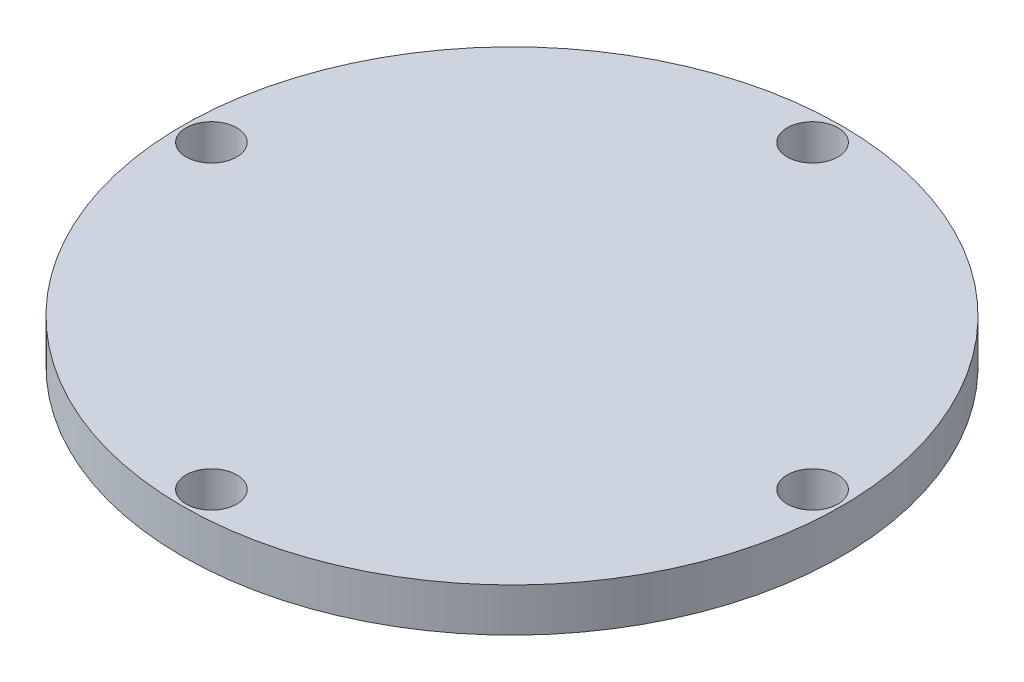
SolidWorks part; units mm, degrees
material "Ceramic Porcelain"
ref_plane "Front Plane" through (0, 0, 0) normal (0, 0, 1) x (1, 0, 0)
ref_plane "Top Plane" through (0, 0, 0) normal (0, 1, 0) x (1, 0, 0)
ref_plane "Right Plane" through (0, 0, 0) normal (1, 0, 0) x (0, 0, -1)
ref_axis "Y Axis" through (0, 0.0762, 0) along (0, -1, 0)
sketch "outter" plane through (0, 0, 0) normal (0, 1, 0) x (1, 0, 0)
  circle A0 centre (0, 0) radius 11.557
  dimension "D1" = 23.114
extrude "Body" add sketch "outter" against normal blind 1.524
sketch "Screw Position" plane through (0, 0, 0) normal (0, 1, 0) x (1, 0, 0)
  point P0 (0, 10.541)
  dimension "D1" = 10.541
hole_wizard "#0 Clearance Hole" positions "Sketch11" profile "Sketch12" hole size "#0" standard "ANSI Inch"
sketch "Sketch11" plane through (0, 0, 0) normal (0, 1, 0) x (-1, 0, 0)
  point P0 (0, -10.541)
sketch "Sketch12" plane through (0, 0, -10.541) normal (1, 0, 0) x (0, 0, 1)
  line L0 (0, 0) -> (0, 2.0582)
  line L1 (0, 2.0582) -> (0.889, 1.524)
  line L2 (0.889, 1.524) -> (0.889, 0)
  line L5 (0.889, 0) -> (0, 0)
  line L10 (0, 2.0582) -> (-0.889, 1.524) construction
  line L11 (0, -6.35) -> (0, 107.95) construction
  dimension "Hole Dia." = 1.778
  dimension "Hole Depth" = 1.524
  dimension "Drill Angle" = 118
pattern_circular "Screw Holes" count 4 over 360 about axis through (0, 0.0762, 0) along (0, -1, 0) of "#0 Clearance Hole"
sketch "Sketch13" plane through (0, 0, 0) normal (0, 1, 0) x (1, 0, 0)
  point P0 (-3.8881, 9.3866)
  point P1 (3.8881, 9.3866)
  point P5 (9.3866, 3.8881)
  point P6 (9.3866, -3.8881)
  point P7 (3.8881, -9.3866)
  point P8 (-3.8881, -9.3866)
  point P9 (-9.3866, -3.8881)
  point P10 (-9.3866, 3.8881)
  point P11 (0, 0)
  dimension "D1" = 10.16
  dimension "D2" = 8
equation "\"mount_d\"= 0.91in"
equation "\"dieletric_h\"= 0.06in"
equation "\"D1@outter\" = \"mount_d\""
equation "\"D1@Body\" = \"dieletric_h\""
equation "\"screw_inner_r\"= 0.415in"
equation "\"io_r\"= 0.4in"
equation "\"D1@Screw Position\" = \"screw_inner_r\""
equation "\"D1@Sketch13\"=\"io_r\""
